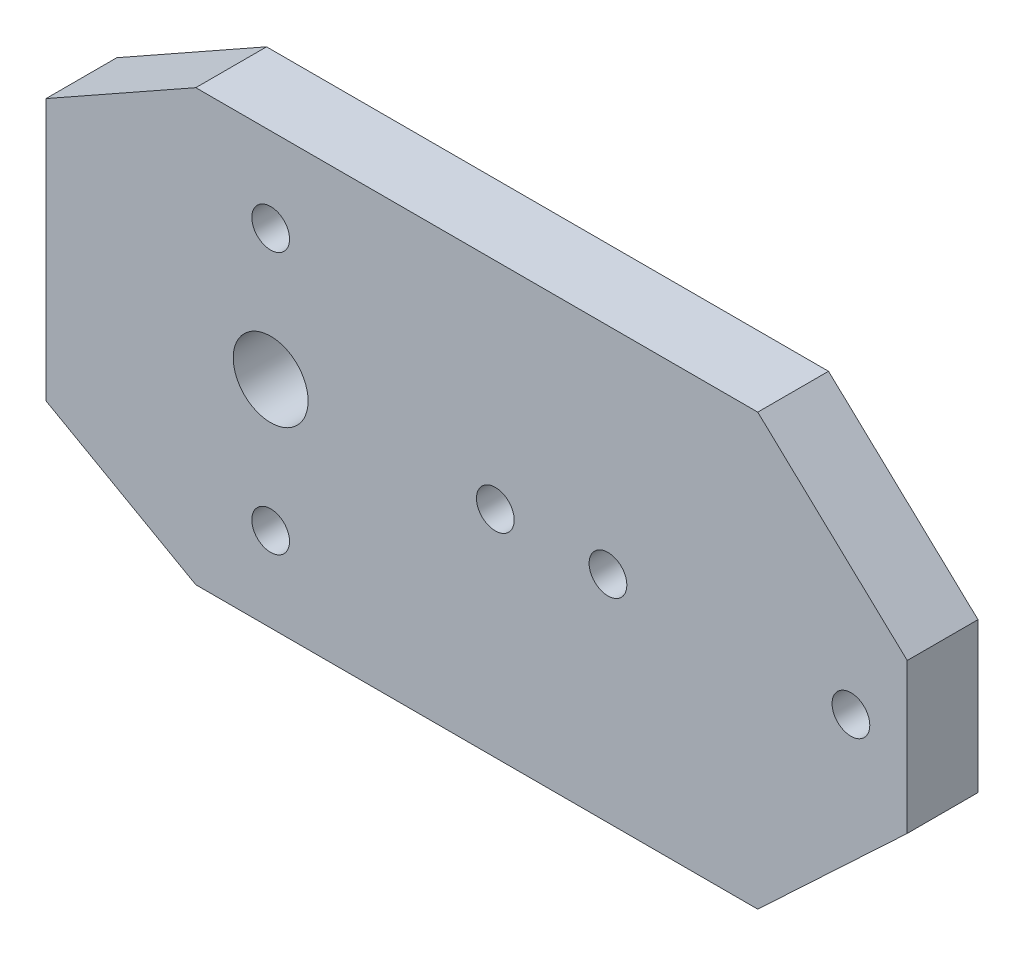
SolidWorks part; units mm, degrees
ref_plane "Front Plane" through (0, 0, 0) normal (0, 0, 1) x (1, 0, 0)
ref_plane "Top Plane" through (0, 0, 0) normal (0, 1, 0) x (1, 0, 0)
ref_plane "Right Plane" through (0, 0, 0) normal (1, 0, 0) x (0, 0, -1)
sketch "Sketch1" plane through (0, 0, 0) normal (0, 0, 1) x (1, 0, 0)
  line L0 (-19.05, -11.1) -> (-6.35, -18.25)
  line L1 (-6.35, -18.25) -> (41.3, -18.25)
  line L2 (41.3, -18.25) -> (53.975, -6.35)
  line L3 (53.975, -6.35) -> (53.975, 6.35)
  line L4 (53.975, 6.35) -> (41.3, 18.25)
  line L5 (41.3, 18.25) -> (-6.35, 18.25)
  line L6 (-6.35, 18.25) -> (-19.05, 11.1)
  line L7 (-19.05, 11.1) -> (-19.05, -11.1)
  circle A0 centre (19.05, 0) radius 1.6
  circle A1 centre (28.6, 0) radius 1.6
  circle A2 centre (49.2, 0) radius 1.6
  circle A3 centre (0, 0) radius 3.175
  circle A4 centre (0, 11.1) radius 1.6
  circle A5 centre (0, -11.1) radius 1.6
extrude "Boss-Extrude1" add sketch "Sketch1" along normal blind 6
ref_axis "Pivot" through (0, 0, 6.3) along (0, 0, -1)
ref_plane "LinkPin_px" through (19.05, 0, 0) normal (1, 0, 0) x (0, 0, -1)
ref_axis "LinkPin" through (19.05, 0, 6.3) along (0, 0, -1)
